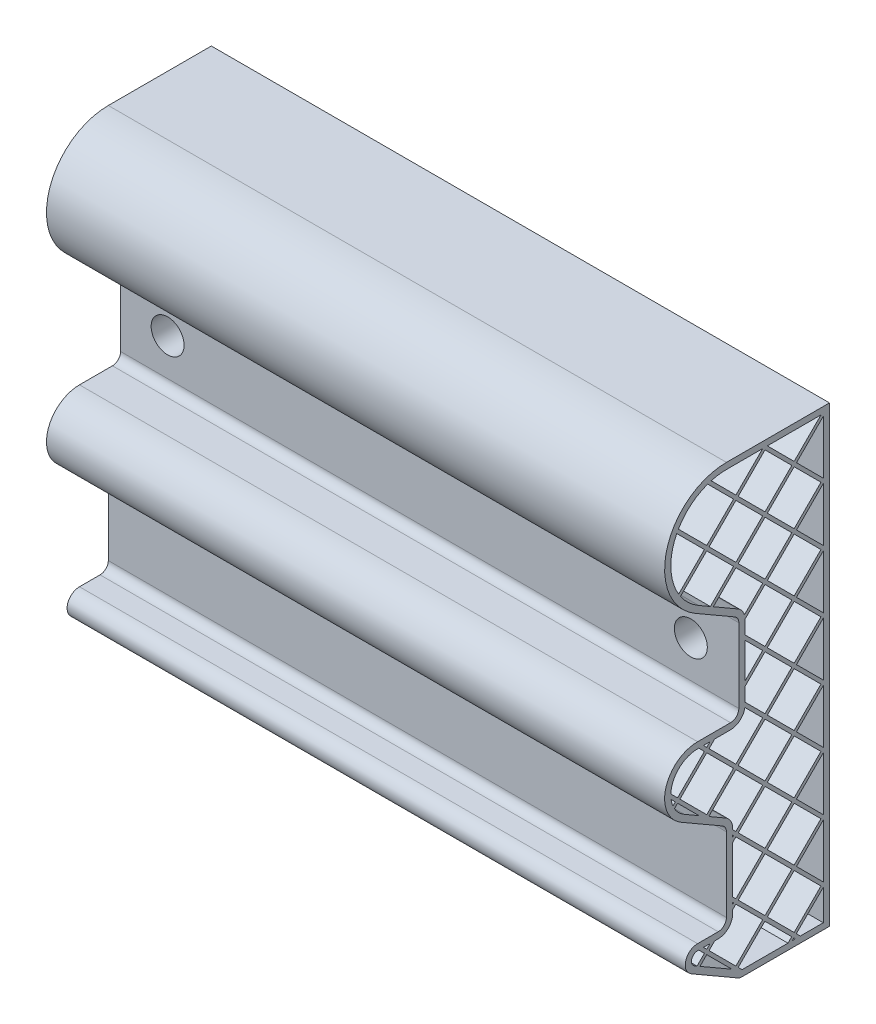
SolidWorks part; units mm, degrees
ref_plane "Front" through (0, 0, 0) normal (0, 0, 1) x (1, 0, 0)
ref_plane "Top" through (0, 0, 0) normal (0, 1, 0) x (1, 0, 0)
ref_plane "Right" through (0, 0, 0) normal (1, 0, 0) x (0, 0, -1)
sketch "Croquis1" plane through (0, 0, 0) normal (1, 0, 0) x (0, 0, -1)
  line L1 (0, 0) -> (-21.2539, 0)
  line L2 (0, 0) -> (0, 110)
  line L3 (0, 110) -> (-25, 110)
  line L5 (-32, 54.7927) -> (-24, 54.7927)
  line L10 (-22, 74.7927) -> (-22, 56.7927)
  line L14 (-25, 14.359) -> (-25, 32.359)
  line L16 (-36, 39.8645) -> (-26, 34.091)
  line L17 (-32, 12.359) -> (-27, 12.359)
  line L18 (-32.5, 82.0096) -> (-23, 76.5248)
  line L19 (-33.5, 6.7609) -> (-22.2539, 0.2679)
  arc A2 (-25, 110) -> (-32.5, 82.0096) centre (-25, 95) ccw
  arc A3 (-32, 12.359) -> (-33.5, 6.7609) centre (-32, 9.359) ccw
  arc A6 (-32, 54.7927) -> (-36, 39.8645) centre (-32, 46.7927) ccw
  arc A8 (-23, 76.5248) -> (-22, 74.7927) centre (-24, 74.7927) cw
  arc A9 (-22, 56.7927) -> (-24, 54.7927) centre (-24, 56.7927) cw
  arc A10 (-26, 34.091) -> (-25, 32.359) centre (-27, 32.359) cw
  arc A11 (-25, 14.359) -> (-27, 12.359) centre (-27, 14.359) cw
  arc A12 (-21.2539, 0) -> (-22.2539, 0.2679) centre (-21.2539, 2) cw
  point P0 (0, 0)
  point P11 (-22, 54.7927)
  dimension "D1" = 2
  dimension "D2" = 15
  dimension "D8" = 8
  dimension "D9" = 30
  dimension "D12" = 2
  dimension "D7" = 2
  dimension "D10" = 2
  dimension "D11" = 2
  dimension "D16" = 40
  dimension "D19" = 110
  dimension "D14" = 10
  dimension "D6" = 3
  dimension "D3" = 40
  dimension "D4" = 30
  dimension "D5" = 18
  dimension "D13" = 30
  dimension "D15" = 15
  dimension "D17" = 20
  dimension "D18" = 20
extrude "Saliente-Extruir1" add sketch "Croquis1" along normal blind 150
sketch "Croquis2" plane through (150, 0, 0) normal (1, 0, 0) x (0, 0, -1)
  line L30 (-24, 53.2927) -> (-32, 53.2927)
  line L31 (-35.25, 41.1636) -> (-25.25, 35.3901)
  line L32 (-23.5, 32.359) -> (-23.5, 14.359)
  line L33 (-27, 10.859) -> (-32, 10.859)
  line L34 (-32.75, 8.0599) -> (-21.5039, 1.567)
  line L35 (-21.2539, 1.5) -> (-1.5, 1.5)
  line L36 (-1.5, 1.5) -> (-1.5, 108.5)
  line L37 (-1.5, 108.5) -> (-25, 108.5)
  line L38 (-31.75, 83.3087) -> (-22.25, 77.8238)
  line L39 (-20.5, 74.7927) -> (-20.5, 56.7927)
  line L40 (-24, 53.2927) -> (-32, 53.2927)
  line L41 (-35.25, 41.1636) -> (-25.25, 35.3901)
  line L42 (-23.5, 32.359) -> (-23.5, 14.359)
  line L43 (-27, 10.859) -> (-32, 10.859)
  line L44 (-32.75, 8.0599) -> (-21.5039, 1.567)
  line L45 (-21.2539, 1.5) -> (-1.5, 1.5)
  line L46 (-1.5, 1.5) -> (-1.5, 108.5)
  line L47 (-1.5, 108.5) -> (-25, 108.5)
  line L48 (-31.75, 83.3087) -> (-22.25, 77.8238)
  line L49 (-20.5, 74.7927) -> (-20.5, 56.7927)
  arc A24 (-24, 53.2927) -> (-20.5, 56.7927) centre (-24, 56.7927) ccw
  arc A25 (-32, 53.2927) -> (-35.25, 41.1636) centre (-32, 46.7927) ccw
  arc A26 (-23.5, 32.359) -> (-25.25, 35.3901) centre (-27, 32.359) ccw
  arc A27 (-27, 10.859) -> (-23.5, 14.359) centre (-27, 14.359) ccw
  arc A28 (-32, 10.859) -> (-32.75, 8.0599) centre (-32, 9.359) ccw
  arc A29 (-21.5039, 1.567) -> (-21.2539, 1.5) centre (-21.2539, 2) ccw
  arc A30 (-25, 108.5) -> (-31.75, 83.3087) centre (-25, 95) ccw
  arc A31 (-20.5, 74.7927) -> (-22.25, 77.8238) centre (-24, 74.7927) ccw
  arc A32 (-24, 53.2927) -> (-20.5, 56.7927) centre (-24, 56.7927) ccw
  arc A33 (-32, 53.2927) -> (-35.25, 41.1636) centre (-32, 46.7927) ccw
  arc A34 (-23.5, 32.359) -> (-25.25, 35.3901) centre (-27, 32.359) ccw
  arc A35 (-27, 10.859) -> (-23.5, 14.359) centre (-27, 14.359) ccw
  arc A36 (-32, 10.859) -> (-32.75, 8.0599) centre (-32, 9.359) ccw
  arc A37 (-21.5039, 1.567) -> (-21.2539, 1.5) centre (-21.2539, 2) ccw
  arc A38 (-25, 108.5) -> (-31.75, 83.3087) centre (-25, 95) ccw
  arc A39 (-20.5, 74.7927) -> (-22.25, 77.8238) centre (-24, 74.7927) ccw
  dimension "D1" = 1.5
sketch "Croquis3" plane through (150, 0, 0) normal (1, 0, 0) x (0, 0, -1)
  line L0 (-29.1353, 107.851) -> (-1.5, 80.2157)
  line L1 (-1.5, 108.5) -> (-25, 108.5) construction
  line L2 (-15.6421, 108.5) -> (-1.5, 94.3579)
  line L3 (-1.5, 1.5) -> (-1.5, 108.5) construction
  line L4 (-36.8654, 101.439) -> (-1.5, 66.0736)
  line L5 (-1.5, 51.9315) -> (-20.5, 70.9315)
  line L6 (-1.5, 37.7893) -> (-20.5, 56.7893)
  line L7 (-1.5, 23.6472) -> (-31.1456, 53.2927)
  line L8 (-1.5, 9.5051) -> (-38.4933, 46.4984)
  line L9 (-7.6371, 1.5) -> (-23.5, 17.3629)
  line L10 (-21.2539, 1.5) -> (-1.5, 1.5) construction
  line L11 (-20.5, 74.7927) -> (-20.5, 56.7927) construction
  line L12 (-24, 53.2927) -> (-32, 53.2927) construction
  line L13 (-23.5, 32.359) -> (-23.5, 14.359) construction
  line L14 (-22.3139, 2.0346) -> (-31.1382, 10.859)
  line L15 (-32.75, 8.0599) -> (-21.5039, 1.567) construction
  line L16 (-27, 10.859) -> (-32, 10.859) construction
  line L17 (-1.5, 108.5) -> (-28.5429, 81.4571)
  line L18 (-36.3896, 87.7525) -> (-15.6421, 108.5)
  line L19 (-20.5397, 75.3182) -> (-1.5, 94.3579)
  line L20 (-37.8191, 43.8966) -> (-1.5, 80.2157)
  line L21 (-29.6457, 37.9279) -> (-1.5, 66.0736)
  line L22 (-23.5, 29.9315) -> (-1.5, 51.9315)
  line L23 (-31.786, 7.5034) -> (-1.5, 37.7893)
  line L24 (-22.8202, 2.327) -> (-1.5, 23.6472)
  line L25 (-9.5051, 1.5) -> (-1.5, 9.5051)
  line L26 (-31.75, 83.3087) -> (-22.25, 77.8238) construction
  line L27 (-35.25, 41.1636) -> (-25.25, 35.3901) construction
  arc A0 (-25, 108.5) -> (-31.75, 83.3087) centre (-25, 95) ccw construction
  arc A1 (-24, 53.2927) -> (-20.5, 56.7927) centre (-24, 56.7927) ccw construction
  arc A2 (-32, 53.2927) -> (-35.25, 41.1636) centre (-32, 46.7927) ccw construction
  arc A3 (-20.5, 74.7927) -> (-22.25, 77.8238) centre (-24, 74.7927) ccw construction
  point P29 (-36.5148, 87.9531)
  point P42 (-1.1586, 79.8835)
  point P51 (-1.5, 65.7785)
  point P53 (-1.8488, 51.9315)
  point P55 (-1.5, 37.2719)
  point P57 (-1.1567, 23.6472)
  point P59 (-1.5, 9.1013)
  point P61 (-9.5796, 1.5)
  point P62 (0, 0)
  point P63 (-28.4987, 81.4315)
  point P66 (-31.1456, 69.1928)
  point P67 (-1.1747, 94.6832)
  point P68 (-24.6395, 0.5076)
  point P69 (-22.8202, 2.327)
  point P70 (-31.787, 7.5039)
  point P71 (-23.5, 29.985)
  point P72 (-29.4056, 37.7893)
  point P75 (-37.8171, 43.8925)
  point P76 (-20.5368, 75.2992)
  dimension "D1" = 45
  dimension "D2" = 10
  dimension "D4" = 10
  dimension "D5" = 10
  dimension "D6" = 10
  dimension "D7" = 10
  dimension "D8" = 10
  dimension "D9" = 10
  dimension "D10" = 10
  dimension "D11" = 45
  dimension "D12" = 10
sketch "Croquis4" plane through (150, 0, 0) normal (1, 0, 0) x (0, 0, -1)
  line L68 (-22.8202, 2.327) -> (-1.5, 23.6472) construction
  line L69 (-9.5051, 1.5) -> (-1.5, 9.5051) construction
  line L70 (-22.3139, 2.0346) -> (-31.1382, 10.859) construction
  line L71 (-7.6371, 1.5) -> (-23.5, 17.3629) construction
  line L72 (-31.786, 7.5034) -> (-1.5, 37.7893) construction
  line L73 (-1.5, 9.5051) -> (-38.4933, 46.4984) construction
  line L74 (-1.5, 23.6472) -> (-31.1456, 53.2927) construction
  line L75 (-1.5, 37.7893) -> (-20.5, 56.7893) construction
  line L76 (-29.6457, 37.9279) -> (-1.5, 66.0736) construction
  line L77 (-1.5, 51.9315) -> (-20.5, 70.9315) construction
  line L78 (-37.8191, 43.8966) -> (-1.5, 80.2157) construction
  line L79 (-20.5397, 75.3182) -> (-1.5, 94.3579) construction
  line L80 (-1.5, 108.5) -> (-28.5429, 81.4571) construction
  line L81 (-15.6421, 108.5) -> (-1.5, 94.3579) construction
  line L82 (-36.3896, 87.7525) -> (-15.6421, 108.5) construction
  line L83 (-36.8654, 101.439) -> (-1.5, 66.0736) construction
  line L84 (-29.1353, 107.851) -> (-1.5, 80.2157) construction
  line L119 (-23.5, 29.9315) -> (-1.5, 51.9315) construction
  line L120 (-1.5, 51.9315) -> (-20.5, 70.9315)
  line L121 (-23.5, 29.9315) -> (-1.5, 51.9315)
  line L122 (-36.8654, 101.439) -> (-1.5, 66.0736)
  line L123 (-29.6457, 37.9279) -> (-1.5, 66.0736)
  line L124 (-29.1353, 107.851) -> (-1.5, 80.2157)
  line L125 (-37.8191, 43.8966) -> (-1.5, 80.2157)
  line L126 (-20.5397, 75.3182) -> (-1.5, 94.3579)
  line L127 (-15.6421, 108.5) -> (-1.5, 94.3579)
  line L128 (-36.3896, 87.7525) -> (-15.6421, 108.5)
  line L129 (-7.6371, 1.5) -> (-23.5, 17.3629)
  line L130 (-1.5, 9.5051) -> (-38.4933, 46.4984)
  line L131 (-9.5051, 1.5) -> (-1.5, 9.5051)
  line L132 (-1.5, 23.6472) -> (-31.1456, 53.2927)
  line L133 (-22.8202, 2.327) -> (-1.5, 23.6472)
  line L134 (-1.5, 37.7893) -> (-20.5, 56.7893)
  line L135 (-31.786, 7.5034) -> (-1.5, 37.7893)
  line L136 (-1.5, 108.5) -> (-28.5429, 81.4571)
  line L137 (-22.3139, 2.0346) -> (-31.1382, 10.859)
  line L138 (-36.1068, 87.4697) -> (-15.6421, 107.9343)
  line L139 (-15.6421, 107.9343) -> (-2.0657, 94.3579)
  line L140 (-20.8225, 75.601) -> (-2.0657, 94.3579)
  line L141 (-29.4182, 107.5682) -> (-2.0657, 80.2157)
  line L142 (-38.102, 44.1794) -> (-2.0657, 80.2157)
  line L143 (-37.1483, 101.1562) -> (-1.7828, 65.7908)
  line L144 (-1.7828, 108.7828) -> (-28.8258, 81.7399)
  line L145 (-36.6725, 88.0353) -> (-15.6421, 109.0657)
  line L146 (-15.6421, 109.0657) -> (-0.9343, 94.3579)
  line L147 (-20.2568, 75.0354) -> (-0.9343, 94.3579)
  line L148 (-28.8525, 108.1339) -> (-0.9343, 80.2157)
  line L149 (-37.5363, 43.6138) -> (-0.9343, 80.2157)
  line L150 (-36.5826, 101.7219) -> (-1.2172, 66.3564)
  line L151 (-1.2172, 108.2172) -> (-28.2601, 81.1742)
  line L152 (-23.2172, 29.6486) -> (-0.9343, 51.9315)
  line L153 (-0.9343, 51.9315) -> (-20.2172, 71.2143)
  line L154 (-29.3628, 37.6451) -> (-1.2172, 65.7908)
  line L155 (-1.2172, 38.0722) -> (-20.2172, 57.0722)
  line L156 (-1.2172, 23.93) -> (-30.8627, 53.5756)
  line L157 (-23.7828, 30.2143) -> (-2.0657, 51.9315)
  line L158 (-2.0657, 51.9315) -> (-20.7828, 70.6486)
  line L159 (-29.9285, 38.2108) -> (-1.7828, 66.3564)
  line L160 (-1.7828, 37.5065) -> (-20.7828, 56.5065)
  line L161 (-1.7828, 23.3643) -> (-31.4284, 53.0099)
  line L162 (-9.2222, 1.2172) -> (-0.9343, 9.5051)
  line L163 (-0.9343, 9.5051) -> (-38.2105, 46.7812)
  line L164 (-31.5031, 7.2205) -> (-1.2172, 37.5065)
  line L165 (-22.5374, 2.0441) -> (-1.2172, 23.3643)
  line L166 (-7.3542, 1.7828) -> (-23.2172, 17.6458)
  line L167 (-22.031, 2.3175) -> (-30.8554, 11.1418)
  line L168 (-9.7879, 1.7828) -> (-2.0657, 9.5051)
  line L169 (-2.0657, 9.5051) -> (-38.7762, 46.2155)
  line L170 (-32.0688, 7.7862) -> (-1.7828, 38.0722)
  line L171 (-23.1031, 2.6098) -> (-1.7828, 23.93)
  line L172 (-7.9199, 1.2172) -> (-23.7828, 17.0801)
  line L173 (-22.5967, 1.7518) -> (-31.421, 10.5761)
  dimension "D1" = 0.4
  dimension "D2" = 0.4
  dimension "D3" = 0.4
  dimension "D4" = 0.4
  dimension "D5" = 0.4
  dimension "D6" = 0.4
sketch "Croquis5" plane through (150, 0, 0) normal (1, 0, 0) x (0, 0, -1)
  line L0 (-31.4273, 7.2963) -> (-23.6523, 2.8074)
  line L1 (-9.7879, 1.7828) -> (-2.0657, 9.5051) construction
  line L2 (-22.5967, 1.7518) -> (-31.421, 10.5761) construction
  line L3 (-22.031, 2.3175) -> (-30.8554, 11.1418) construction
  line L4 (-22.5374, 2.0441) -> (-1.2172, 23.3643) construction
  line L5 (-23.1031, 2.6098) -> (-1.7828, 23.93) construction
  line L6 (-7.3542, 1.7828) -> (-23.2172, 17.6458) construction
  line L7 (-31.7039, 10.859) -> (-32, 10.859)
  line L8 (-32.0688, 7.7862) -> (-1.7828, 38.0722) construction
  line L9 (-31.5031, 7.2205) -> (-1.2172, 37.5065) construction
  line L10 (-2.0657, 9.5051) -> (-38.7762, 46.2155) construction
  line L11 (-0.9343, 9.5051) -> (-38.2105, 46.7812) construction
  line L12 (-23.2172, 29.6486) -> (-0.9343, 51.9315) construction
  line L13 (-23.7828, 30.2143) -> (-2.0657, 51.9315) construction
  line L14 (-1.7828, 23.3643) -> (-31.4284, 53.0099) construction
  line L15 (-1.2172, 23.93) -> (-30.8627, 53.5756) construction
  line L16 (-1.7828, 37.5065) -> (-20.7828, 56.5065) construction
  line L17 (-1.2172, 38.0722) -> (-20.2172, 57.0722) construction
  line L18 (-29.9285, 38.2108) -> (-1.7828, 66.3564) construction
  line L19 (-29.3628, 37.6451) -> (-1.2172, 65.7908) construction
  line L20 (-0.9343, 51.9315) -> (-20.2172, 71.2143) construction
  line L21 (-2.0657, 51.9315) -> (-20.7828, 70.6486) construction
  line L22 (-37.5363, 43.6138) -> (-0.9343, 80.2157) construction
  line L23 (-38.102, 44.1794) -> (-2.0657, 80.2157) construction
  line L24 (-20.2568, 75.0354) -> (-0.9343, 94.3579) construction
  line L25 (-20.8225, 75.601) -> (-2.0657, 94.3579) construction
  line L26 (-1.2172, 108.2172) -> (-28.2601, 81.1742) construction
  line L27 (-1.7828, 108.7828) -> (-28.8258, 81.7399) construction
  line L28 (-15.6421, 107.9343) -> (-2.0657, 94.3579) construction
  line L29 (-15.6421, 109.0657) -> (-0.9343, 94.3579) construction
  line L30 (-36.1068, 87.4697) -> (-15.6421, 107.9343) construction
  line L31 (-36.6725, 88.0353) -> (-15.6421, 109.0657) construction
  line L32 (-37.1483, 101.1562) -> (-1.7828, 65.7908) construction
  line L33 (-36.5826, 101.7219) -> (-1.2172, 66.3564) construction
  line L34 (-28.8525, 108.1339) -> (-0.9343, 80.2157) construction
  line L35 (-29.4182, 107.5682) -> (-2.0657, 80.2157) construction
  line L36 (-28.996, 10.859) -> (-30.5725, 10.859)
  line L37 (-10.0707, 1.5) -> (-9.1719, 2.3988)
  line L38 (-23.6523, 2.8074) -> (-29.7843, 8.9394)
  line L39 (-21.2135, 1.5) -> (-22.1475, 2.434)
  line L40 (-22.1475, 2.434) -> (-15.6773, 8.9042)
  line L41 (-22.7132, 2.9997) -> (-16.2078, 9.5051)
  line L42 (-7.0714, 1.5) -> (-8.0499, 2.4785)
  line L43 (-23.5, 16.355) -> (-23.2789, 16.5761)
  line L44 (-32.1446, 7.7104) -> (-30.35, 9.5051)
  line L45 (-31.4273, 7.2963) -> (-29.7843, 8.9394)
  line L46 (-2.0657, 9.5051) -> (-8.5711, 16.0104)
  line L47 (-1.5, 10.0707) -> (-8.0054, 16.5761)
  line L48 (-23.5, 29.3658) -> (-22.7132, 30.1526)
  line L49 (-23.5, 30.4971) -> (-23.2789, 30.7183)
  line L50 (-2.0657, 23.6472) -> (-8.5711, 30.1526)
  line L51 (-1.5, 24.2129) -> (-8.0054, 30.7183)
  line L52 (-2.0657, 37.7893) -> (-8.5711, 44.2947)
  line L53 (-1.5, 38.355) -> (-8.0054, 44.8604)
  line L54 (-29.7843, 38.355) -> (-23.2789, 44.8604)
  line L55 (-29.2186, 37.7893) -> (-22.7132, 44.2947)
  line L56 (-1.5, 52.4971) -> (-8.0054, 59.0025)
  line L57 (-2.0657, 51.9315) -> (-8.5711, 58.4368)
  line L58 (-37.6211, 43.5289) -> (-36.8553, 44.2947)
  line L59 (-37.9967, 44.2847) -> (-37.421, 44.8604)
  line L60 (-20.5, 74.7922) -> (-15.6421, 79.65)
  line L61 (-20.6424, 75.7811) -> (-16.2078, 80.2157)
  line L62 (-1.5, 107.9343) -> (-8.0054, 101.4289)
  line L63 (-2.0657, 108.5) -> (-8.5711, 101.9946)
  line L64 (-15.6421, 107.9343) -> (-9.1368, 101.4289)
  line L65 (-15.0765, 108.5) -> (-8.5711, 101.9946)
  line L66 (-36.1652, 87.4113) -> (-29.7843, 93.7922)
  line L67 (-36.6051, 88.1027) -> (-30.35, 94.3579)
  line L68 (-37.0596, 101.0675) -> (-30.35, 94.3579)
  line L69 (-36.6617, 101.801) -> (-29.7843, 94.9235)
  line L70 (-28.7013, 107.9827) -> (-22.7132, 101.9946)
  line L71 (-29.5574, 107.7075) -> (-23.2789, 101.4289)
  line L72 (-22.7132, 101.9946) -> (-16.2078, 108.5)
  line L73 (-22.1475, 101.4289) -> (-15.6421, 94.9235)
  line L74 (-22.1475, 101.4289) -> (-15.6421, 107.9343)
  line L75 (-22.7132, 100.8632) -> (-16.2078, 94.3579)
  line L76 (-29.7843, 94.9235) -> (-23.2789, 101.4289)
  line L77 (-29.7843, 93.7922) -> (-23.2789, 87.2868)
  line L78 (-29.2186, 94.3579) -> (-22.7132, 87.8525)
  line L79 (-29.2186, 94.3579) -> (-22.7132, 100.8632)
  line L80 (-16.2078, 94.3579) -> (-22.7132, 87.8525)
  line L81 (-15.0765, 94.3579) -> (-8.5711, 87.8525)
  line L82 (-15.6421, 93.7922) -> (-22.1475, 87.2868)
  line L83 (-15.6421, 93.7922) -> (-9.1368, 87.2868)
  line L84 (-9.1368, 101.4289) -> (-15.6421, 94.9235)
  line L85 (-8.0054, 101.4289) -> (-1.5, 94.9235)
  line L86 (-8.5711, 100.8632) -> (-2.0657, 94.3579)
  line L87 (-8.5711, 100.8632) -> (-15.0765, 94.3579)
  line L88 (-8.5711, 87.8525) -> (-2.0657, 94.3579)
  line L89 (-8.0054, 87.2868) -> (-1.5, 80.7814)
  line L90 (-8.0054, 87.2868) -> (-1.5, 93.7922)
  line L91 (-8.5711, 86.7211) -> (-2.0657, 80.2157)
  line L92 (-23.2789, 87.2868) -> (-28.9016, 81.6641)
  line L93 (-22.7132, 86.7211) -> (-16.2078, 80.2157)
  line L94 (-22.1475, 87.2868) -> (-15.6421, 80.7814)
  line L95 (-22.7132, 86.7211) -> (-28.1843, 81.25)
  line L96 (-15.6421, 80.7814) -> (-9.1368, 87.2868)
  line L97 (-15.6421, 79.65) -> (-9.1368, 73.1447)
  line L98 (-15.0765, 80.2157) -> (-8.5711, 73.7103)
  line L99 (-15.0765, 80.2157) -> (-8.5711, 86.7211)
  line L100 (-8.5711, 73.7103) -> (-2.0657, 80.2157)
  line L101 (-8.5711, 72.579) -> (-2.0657, 66.0736)
  line L102 (-8.0054, 73.1447) -> (-1.5, 66.6393)
  line L103 (-8.0054, 73.1447) -> (-1.5, 79.65)
  line L104 (-15.6421, 66.6393) -> (-9.1368, 73.1447)
  line L105 (-16.2078, 66.0736) -> (-20.5, 70.3658)
  line L106 (-15.6421, 66.6393) -> (-20.5, 71.4971)
  line L107 (-15.0765, 66.0736) -> (-8.5711, 72.579)
  line L108 (-8.5711, 59.5682) -> (-2.0657, 66.0736)
  line L109 (-9.1368, 59.0025) -> (-15.6421, 65.5079)
  line L110 (-8.5711, 59.5682) -> (-15.0765, 66.0736)
  line L111 (-8.0054, 59.0025) -> (-1.5, 65.5079)
  line L112 (-15.6421, 52.4971) -> (-9.1368, 59.0025)
  line L113 (-15.6421, 52.4971) -> (-20.5, 57.355)
  line L114 (-16.2078, 51.9315) -> (-20.5402, 56.2638)
  line L115 (-15.0765, 51.9315) -> (-8.5711, 58.4368)
  line L116 (-29.7843, 52.4971) -> (-28.9887, 53.2927)
  line L117 (-30.35, 51.9315) -> (-31.7112, 53.2927)
  line L118 (-29.7843, 52.4971) -> (-30.5799, 53.2927)
  line L119 (-29.2186, 51.9315) -> (-27.8573, 53.2927)
  line L120 (-36.8553, 45.4261) -> (-30.35, 51.9315)
  line L121 (-37.421, 44.8604) -> (-38.4348, 45.8741)
  line L122 (-36.8553, 45.4261) -> (-38.4943, 47.065)
  line L123 (-36.2897, 44.8604) -> (-29.7843, 51.3658)
  line L124 (-29.7843, 38.355) -> (-36.2897, 44.8604)
  line L125 (-22.7132, 31.2839) -> (-16.2078, 37.7893)
  line L126 (-22.7132, 31.2839) -> (-23.5, 32.0707)
  line L127 (-22.1475, 30.7183) -> (-15.6421, 37.2236)
  line L128 (-23.2789, 30.7183) -> (-23.5, 30.9394)
  line L129 (-15.6421, 38.355) -> (-9.1368, 44.8604)
  line L130 (-15.6421, 38.355) -> (-22.1475, 44.8604)
  line L131 (-15.0765, 37.7893) -> (-8.5711, 44.2947)
  line L132 (-16.2078, 37.7893) -> (-22.7132, 44.2947)
  line L133 (-8.5711, 31.2839) -> (-2.0657, 37.7893)
  line L134 (-8.5711, 31.2839) -> (-15.0765, 37.7893)
  line L135 (-8.0054, 30.7183) -> (-1.5, 37.2236)
  line L136 (-9.1368, 30.7183) -> (-15.6421, 37.2236)
  line L137 (-15.6421, 24.2129) -> (-9.1368, 30.7183)
  line L138 (-15.6421, 24.2129) -> (-22.1475, 30.7183)
  line L139 (-15.0765, 23.6472) -> (-8.5711, 30.1526)
  line L140 (-16.2078, 23.6472) -> (-22.7132, 30.1526)
  line L141 (-8.5711, 17.1418) -> (-2.0657, 23.6472)
  line L142 (-8.5711, 17.1418) -> (-15.0765, 23.6472)
  line L143 (-8.0054, 16.5761) -> (-1.5, 23.0815)
  line L144 (-9.1368, 16.5761) -> (-15.6421, 23.0815)
  line L145 (-22.7132, 17.1418) -> (-16.2078, 23.6472)
  line L146 (-22.7132, 17.1418) -> (-23.5, 17.9286)
  line L147 (-22.1475, 16.5761) -> (-15.6421, 23.0815)
  line L148 (-23.2789, 16.5761) -> (-23.5, 16.7952)
  line L149 (-15.6421, 10.0707) -> (-9.1368, 16.5761)
  line L150 (-15.6421, 10.0707) -> (-22.1475, 16.5761)
  line L151 (-16.2078, 9.5051) -> (-22.7132, 16.0104)
  line L152 (-15.0765, 9.5051) -> (-8.5711, 16.0104)
  line L153 (-8.5711, 2.9997) -> (-2.0657, 9.5051)
  line L154 (-9.1719, 2.3988) -> (-15.6773, 8.9042)
  line L155 (-8.5711, 2.9997) -> (-15.0765, 9.5051)
  line L156 (-8.0499, 2.4785) -> (-1.5, 8.9394)
  line L157 (-22.7132, 2.9997) -> (-29.2186, 9.5051)
  line L158 (-29.7843, 10.0707) -> (-28.996, 10.859)
  line L159 (-29.7843, 10.0707) -> (-30.5725, 10.859)
  line L160 (-29.2186, 9.5051) -> (-27.8647, 10.859)
  line L161 (-30.35, 9.5051) -> (-31.7039, 10.859)
  line L162 (-8.5711, 45.4261) -> (-2.0657, 51.9315)
  line L163 (-8.0054, 44.8604) -> (-1.5, 51.3658)
  line L164 (-8.5711, 45.4261) -> (-15.0765, 51.9315)
  line L165 (-9.1368, 44.8604) -> (-15.6421, 51.3658)
  line L166 (-22.7132, 45.4261) -> (-16.2078, 51.9315)
  line L167 (-23.2789, 44.8604) -> (-29.7843, 51.3658)
  line L168 (-22.7132, 45.4261) -> (-29.2186, 51.9315)
  line L169 (-22.1475, 44.8604) -> (-15.6421, 51.3658)
  line L170 (-16.2078, 108.5) -> (-25, 108.5)
  line L171 (-1.5, 94.9235) -> (-1.5, 107.9343)
  line L172 (-1.5, 80.7814) -> (-1.5, 93.7922)
  line L173 (-1.5, 66.6393) -> (-1.5, 79.65)
  line L174 (-1.5, 52.4971) -> (-1.5, 65.5079)
  line L175 (-1.5, 38.355) -> (-1.5, 51.3658)
  line L176 (-1.5, 24.2129) -> (-1.5, 37.2236)
  line L177 (-1.5, 10.0707) -> (-1.5, 23.0815)
  line L178 (-7.0714, 1.5) -> (-1.5, 1.5)
  line L179 (-23.5, 15.2236) -> (-22.7132, 16.0104)
  line L180 (-31.75, 83.3087) -> (-22.25, 77.8238)
  line L181 (-20.5, 74.7927) -> (-20.5, 56.7927)
  line L182 (-24, 53.2927) -> (-32, 53.2927)
  line L183 (-35.25, 41.1636) -> (-25.25, 35.3901)
  line L184 (-23.5, 32.359) -> (-23.5, 14.359)
  line L185 (-27, 10.859) -> (-32, 10.859)
  line L186 (-32.75, 8.0599) -> (-21.5039, 1.567)
  line L187 (-21.2539, 1.5) -> (-1.5, 1.5)
  line L188 (-1.5, 1.5) -> (-1.5, 108.5)
  line L189 (-1.5, 108.5) -> (-25, 108.5)
  line L190 (-31.75, 83.3087) -> (-28.9016, 81.6641)
  line L192 (-24, 53.2927) -> (-27.8573, 53.2927)
  line L193 (-35.25, 41.1636) -> (-31.6399, 39.0793)
  line L194 (-23.5, 32.359) -> (-23.5, 32.0707)
  line L195 (-27, 10.859) -> (-27.8647, 10.859)
  line L196 (-32.75, 8.0599) -> (-32.1446, 7.7104)
  line L197 (-21.2135, 1.5) -> (-10.0707, 1.5)
  line L198 (-1.5, 1.5) -> (-1.5, 8.9394)
  line L199 (-2.0657, 108.5) -> (-15.0765, 108.5)
  line L200 (-23.5, 15.2236) -> (-23.5, 14.359)
  line L201 (-8.6549, 1.8818) -> (-8.2731, 1.5)
  line L202 (-8.2731, 1.5) -> (-9.0419, 1.5)
  line L203 (-8.6549, 1.8818) -> (-9.0419, 1.5)
  line L204 (-23.5, 16.7952) -> (-23.5, 16.355)
  line L205 (-23.5, 29.3658) -> (-23.5, 17.9286)
  line L206 (-31.6399, 39.0793) -> (-36.8553, 44.2947)
  line L207 (-28.9631, 37.5338) -> (-29.2186, 37.7893)
  line L208 (-23.5, 30.9394) -> (-23.5, 30.4971)
  line L209 (-28.9631, 37.5338) -> (-25.25, 35.3901)
  line L210 (-28.1843, 81.25) -> (-22.25, 77.8238)
  line L211 (-20.5, 70.3658) -> (-20.5, 61.7814)
  line L212 (-20.5, 61.7814) -> (-16.2078, 66.0736)
  line L213 (-20.5, 60.65) -> (-15.6421, 65.5079)
  line L214 (-20.5, 60.65) -> (-20.5, 57.355)
  line L215 (-28.9887, 53.2927) -> (-30.5799, 53.2927)
  line L216 (-31.7112, 53.2927) -> (-32, 53.2927)
  line L217 (-20.5, 74.7922) -> (-20.5, 71.4971)
  arc A0 (-29.5574, 107.7075) -> (-36.6617, 101.801) centre (-25, 95) ccw
  arc A1 (-37.0596, 101.0675) -> (-36.6051, 88.1027) centre (-25, 95) ccw
  arc A2 (-36.1652, 87.4113) -> (-31.75, 83.3087) centre (-25, 95) ccw
  arc A3 (-38.4348, 45.8741) -> (-37.9967, 44.2847) centre (-32, 46.7927) ccw
  arc A4 (-37.6211, 43.5289) -> (-35.25, 41.1636) centre (-32, 46.7927) ccw
  arc A8 (-20.5, 74.7927) -> (-22.25, 77.8238) centre (-24, 74.7927) ccw
  arc A9 (-24, 53.2927) -> (-20.5, 56.7927) centre (-24, 56.7927) ccw
  arc A10 (-32, 53.2927) -> (-35.25, 41.1636) centre (-32, 46.7927) ccw
  arc A11 (-23.5, 32.359) -> (-25.25, 35.3901) centre (-27, 32.359) ccw
  arc A12 (-27, 10.859) -> (-23.5, 14.359) centre (-27, 14.359) ccw
  arc A13 (-32, 10.859) -> (-32.75, 8.0599) centre (-32, 9.359) ccw
  arc A14 (-21.5039, 1.567) -> (-21.2539, 1.5) centre (-21.2539, 2) ccw
  arc A15 (-25, 108.5) -> (-31.75, 83.3087) centre (-25, 95) ccw
  arc A16 (-20.6424, 75.7811) -> (-22.25, 77.8238) centre (-24, 74.7927) ccw
  arc A17 (-24, 53.2927) -> (-20.5402, 56.2638) centre (-24, 56.7927) ccw
  arc A18 (-32, 53.2927) -> (-38.4943, 47.065) centre (-32, 46.7927) ccw
  arc A19 (-23.5, 32.359) -> (-25.25, 35.3901) centre (-27, 32.359) ccw
  arc A20 (-27, 10.859) -> (-23.5, 14.359) centre (-27, 14.359) ccw
  arc A21 (-32, 10.859) -> (-32.75, 8.0599) centre (-32, 9.359) ccw
  arc A23 (-25, 108.5) -> (-28.7013, 107.9827) centre (-25, 95) ccw
  dimension "D1" = 0
extrude "Cortar-Extruir1" cut sketch "Croquis5" against normal through all
sketch "Croquis6" plane through (0, 0, 22) normal (0, 0, 1) x (1, 0, 0)
  line L0 (0, 65.7927) -> (150, 65.7927) construction
  line L1 (0, 74.7927) -> (0, 56.7927) construction
  line L2 (150, 74.7927) -> (150, 56.7927) construction
  circle A0 centre (11.3917, 65.7927) radius 5
  circle A1 centre (138.3593, 65.7927) radius 5
  dimension "D1" = 10
  dimension "D2" = 10
extrude "Saliente-Extruir2" add sketch "Croquis6" against normal up to surface (22 mm away) contours A0 up to face at (75, 55, 0)
extrude "Saliente-Extruir3" add sketch "Croquis6<3>" against normal up to surface (22 mm away) contours A1 up to face at (75, 55, 0)
sketch "Croquis6<3>" plane through (0, 0, 22) normal (0, 0, 1) x (1, 0, 0) same geometry as "Croquis6"
sketch "Croquis7" plane through (0, 0, 22) normal (0, 0, 1) x (1, 0, 0)
  circle A0 centre (11.3917, 65.7927) radius 2.5
  circle A1 centre (138.3593, 65.7927) radius 2.567
  dimension "D1" = 5
  dimension "D2" = 5.134
extrude "Cortar-Extruir2" cut sketch "Croquis7" against normal up to surface (22 mm away) up to face at (75, 55, 0)
sketch "Croquis8" plane through (0, 0, 22) normal (0, 0, 1) x (1, 0, 0)
  circle A0 centre (11.3917, 65.7927) radius 4
  circle A1 centre (138.3593, 65.7927) radius 4
  dimension "D1" = 8
  dimension "D2" = 8
extrude "Cortar-Extruir3" cut sketch "Croquis8" against normal blind 7
sketch "Croquis9" plane through (0, 0, 0) normal (0, 0, -1) x (-1, 0, 0)
  text T0 "V2"
extrude "Cortar-Extruir4" cut sketch "Croquis9" against normal blind 0.5
